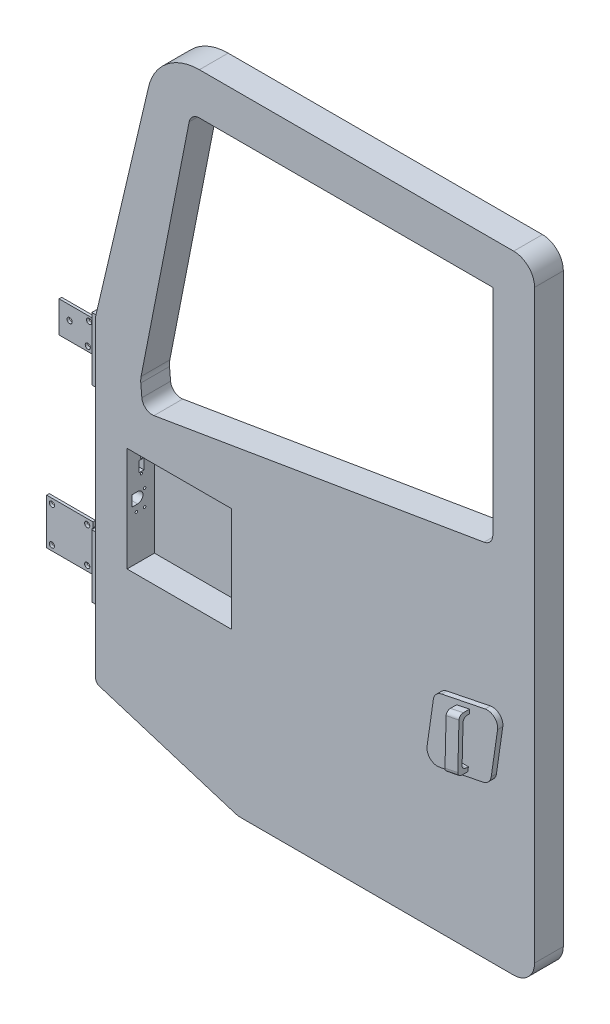
SolidWorks part; units mm, degrees
ref_plane "Front Plane" through (0, 0, 0) normal (0, 0, 1) x (1, 0, 0)
ref_plane "Top Plane" through (0, 0, 0) normal (0, 1, 0) x (1, 0, 0)
ref_plane "Right Plane" through (0, 0, 0) normal (1, 0, 0) x (0, 0, -1)
sketch "Sketch2" plane through (0, 0, 0) normal (0, 0, 1) x (1, 0, 0)
  line L1 (-179.7693, -762.022) -> (482.6, -762.022)
  line L3 (-281.2299, 761.978) -> (482.6, 761.978)
  line L4 (533.4, -711.222) -> (533.4, 711.178)
  line L5 (-459.8603, -656.939) -> (-452.0517, -645.784) construction
  line L6 (-417.9715, 597.0829) -> (44.2876, -63.266) construction
  line L8 (-524.4721, -657.2008) -> (-194.8579, -759.7295)
  line L9 (-306.1723, 639.7777) -> (-423.0219, 45.4039)
  line L10 (-423.7768, 31.1096) -> (-421.1458, 1.4921)
  line L14 (-281.2299, 660.378) -> (431.8, 660.378)
  line L16 (431.7996, 138.4174) -> (431.8, 660.378)
  line L17 (431.8, -660.422) -> (431.8, 660.378) construction
  line L18 (-172.0509, -660.422) -> (431.8, -660.422) construction
  line L19 (-533.4, 116.926) -> (-405.8883, 659.253)
  line L20 (-367.7549, -599.547) -> (-172.0509, -660.422) construction
  line L21 (-55.7209, -79.6007) -> (521.0599, 744.3665) construction
  line L22 (-306.1723, 639.7777) -> (-424.4164, 38.3105) construction
  line L23 (-424.4164, 38.3105) -> (-367.7549, -599.547) construction
  line L24 (-414.3579, -691.4526) -> (-194.8579, -759.7295) construction
  line L25 (-179.7693, -762.022) -> (482.6, -762.022)
  line L27 (-281.2299, 761.978) -> (482.6, 761.978)
  line L28 (533.4, -711.222) -> (533.4, 711.178)
  line L29 (-459.8603, -656.939) -> (-452.0517, -645.784) construction
  line L30 (-417.9715, 597.0829) -> (44.2876, -63.266) construction
  line L31 (-533.4, 116.926) -> (-466.2749, -638.723) construction
  line L32 (-391.6402, -21.3099) -> (410.6048, 113.3679)
  line L33 (-55.7209, -79.6007) -> (521.0599, 744.3665) construction
  line L34 (-281.2299, 761.978) -> (482.6, 761.978)
  line L35 (-533.4, 116.926) -> (-533.4, -645.074)
  line L36 (-179.7693, -762.022) -> (482.6, -762.022)
  line L37 (533.4, 711.178) -> (533.4, -711.222)
  line L38 (-417.9715, 597.0829) -> (44.2876, -63.266) construction
  line L39 (-471.5639, -673.6583) -> (-452.0517, -645.784) construction
  line L40 (-405.8883, 659.253) -> (-528.8132, 33.9764) construction
  line L41 (-55.7209, -79.6007) -> (521.0599, 744.3665) construction
  arc A0 (-405.8883, 659.253) -> (-281.2299, 761.978) centre (-281.2299, 634.978) cw
  arc A3 (533.4, 711.178) -> (482.6, 761.978) centre (482.6, 711.178) ccw
  arc A4 (482.6, -762.022) -> (533.4, -711.222) centre (482.6, -711.222) ccw
  arc A5 (-194.8579, -759.7295) -> (-179.7693, -762.022) centre (-179.7693, -711.222) ccw
  arc A7 (-367.7549, -599.547) -> (-367.7549, -599.547) centre (-367.7549, -599.547) ccw
  arc A8 (-172.0509, -660.422) -> (-172.0509, -660.422) centre (-172.0509, -660.422) ccw
  arc A9 (431.8, -660.422) -> (431.8, -660.422) centre (431.8, -660.422) ccw
  arc A10 (431.8, 660.378) -> (431.8, 660.378) centre (431.8, 660.378) ccw
  arc A11 (-306.1723, 639.7777) -> (-281.2299, 660.378) centre (-281.2299, 634.978) cw
  arc A12 (-423.0219, 45.4039) -> (-423.7768, 31.1096) centre (-373.176, 35.6045) ccw
  arc A13 (-424.4164, 38.3105) -> (-424.4164, 38.3105) centre (-424.4164, 38.3105) ccw construction
  arc A16 (-466.2749, -638.723) -> (-414.3579, -691.4526) centre (-391.0208, -616.5518) ccw construction
  arc A17 (-533.4, -645.074) -> (-524.4721, -657.2008) centre (-520.7, -645.074) ccw
  arc A18 (-528.8132, 33.9764) -> (-533.4, 116.926) centre (-501.9071, 77.0658) ccw construction
  arc A19 (431.7996, 138.4174) -> (410.6048, 113.3679) centre (406.3996, 138.4174) cw
  arc A20 (-391.6402, -21.3099) -> (-421.1458, 1.4921) centre (-395.8454, 3.7395) cw
  point P0 (0, 0)
  point P16 (-533.4, -0.0244)
  point P56 (0, 0)
  point P61 (0, 0)
  dimension "D3" = 127
  dimension "D6" = 50.8
  dimension "D8" = 50.8
  dimension "D2" = 12.7
  dimension "D9" = 25.4
  dimension "D1" = 1066.8
  dimension "D4" = 1524
  dimension "D5" = 762
  dimension "D7" = 101.6
extrude "Boss-Extrude1" add sketch "Sketch2" along normal mid plane 69.85 contours L8 A5 L1 A4 L4 A3 L3 A0 L10 A12 L9 A11 L14 L16 A20 region at (22.1716, -171.0663, 0)
ref_plane "bottom" through (0, -762.022, 0) normal (0, -1, 0) x (-1, 0, 0)
ref_plane "top door check" through (0, -158.772, 0) normal (0, -1, 0) x (-1, 0, 0)
ref_plane "door check mid" through (0, -176.2345, 0) normal (0, -1, 0) x (-1, 0, 0)
ref_plane "bottom door check" through (0, -193.697, 0) normal (0, -1, 0) x (-1, 0, 0)
ref_plane "top hinge top hole" through (0, 66.653, 0) normal (0, -1, 0) x (-1, 0, 0)
ref_plane "top hinge middle hole" through (0, 44.428, 0) normal (0, -1, 0) x (-1, 0, 0)
ref_plane "top hinge bottom hole" through (0, 12.678, 0) normal (0, -1, 0) x (-1, 0, 0)
ref_plane "bottome hinge top hole" through (0, -363.5595, 0) normal (0, -1, 0) x (-1, 0, 0)
ref_plane "bottom hinge bottom hole" through (0, -449.2845, 0) normal (0, -1, 0) x (-1, 0, 0)
ref_plane "Plane1" through (0, 0, 31.75) normal (0, 0, 1) x (1, 0, 0)
sketch "Sketch3" plane through (0, 0, 34.925) normal (0, 0, 1) x (1, 0, 0)
  line L0 (320.1959, -245.101) -> (425.9265, -223.6716)
  line L3 (314.9201, -401.6691) -> (420.6507, -380.2397)
  line L4 (456.113, -252.1835) -> (440.7462, -358.9639)
  line L5 (300.1004, -266.3768) -> (284.7336, -373.1572)
  line L6 (310.4001, -194.8067) -> (287.3499, -354.9772) construction
  line L7 (-487.6326, -408.8312) -> (533.4008, -201.8888) construction
  line L8 (-457.3598, -558.1943) -> (563.6737, -351.2518) construction
  line L9 (461.2461, -216.515) -> (438.1959, -376.6855) construction
  line L10 (373.0612, -234.3863) -> (367.7854, -390.9544) construction
  line L11 (360.2667, -236.9795) -> (354.9908, -393.5476)
  line L12 (385.8558, -231.7931) -> (380.58, -388.3612)
  line L13 (360.3684, -233.9586) -> (355.0926, -390.5267) construction
  line L14 (385.754, -234.814) -> (380.4782, -391.3821) construction
  arc A0 (300.1004, -266.3768) -> (320.1959, -245.101) centre (325.2414, -269.9949) cw
  arc A1 (284.7336, -373.1572) -> (314.9201, -401.6691) centre (309.8746, -376.7752) ccw
  arc A2 (440.7462, -358.9639) -> (420.6507, -380.2397) centre (415.6052, -355.3458) cw
  arc A3 (456.113, -252.1835) -> (425.9265, -223.6716) centre (430.972, -248.5655) ccw
  dimension "D3" = 25.4
  dimension "D1" = 152.4
  dimension "D2" = 152.4
  dimension "D4" = 12.7
  dimension "D5" = 12.7
extrude "Boss-Extrude2" add sketch "Sketch3" along normal blind 12.7 contours L5 A1 L3 L11 L0 A0 | L4 A3 L0 L12 L3 A2 | L12 L0 L11 L3 region at (325.2101, -323.7797, 34.925) region at (370.4233, -312.6704, 34.925) region at (415.6365, -301.561, 34.925)
sketch "Sketch5" plane through (0, 0, 34.925) normal (0, 0, 1) x (1, 0, 0)
  line L6 (-179.7693, -762.022) -> (482.6, -762.022)
  line L12 (-179.7693, -762.022) -> (482.6, -762.022)
  line L28 (387.9598, -243.0291) -> (384.7172, -375.8602)
  line L29 (353.4927, -382.1888) -> (356.7353, -249.3577)
  line L30 (387.9598, -243.0291) -> (356.7353, -249.3577)
  line L31 (384.7172, -375.8602) -> (353.4927, -382.1888)
  line L32 (320.1959, -245.101) -> (425.9265, -223.6716) construction
  line L33 (314.9201, -401.6691) -> (420.6507, -380.2397) construction
  line L34 (320.1959, -245.101) -> (425.9265, -223.6716) construction
  line L35 (314.9201, -401.6691) -> (420.6507, -380.2397) construction
  dimension "D2" = 11.43
  dimension "D3" = 11.43
  dimension "D1" = 0
extrude "Boss-Extrude4" add sketch "Sketch5" along normal blind 38.1 contours L31 L28 L30 L29 region at (370.7262, -312.609, 34.925)
sketch "Sketch6" plane through (393.6581, -9.61, 0) normal (0.9997, -0.0244, 0) x (0, 0, -1)
  line L9 (-47.625, -356.1994) -> (-62.865, -356.1994)
  line L10 (-62.865, -356.1994) -> (-62.865, -243.6487)
  line L11 (-62.865, -243.6487) -> (-47.625, -243.6487)
  line L12 (-47.625, -356.1994) -> (-62.865, -356.1994)
  line L13 (-62.865, -356.1994) -> (-62.865, -243.6487)
  line L14 (-62.865, -243.6487) -> (-47.625, -243.6487)
  line M5 (-47.625, -366.3594) -> (-47.625, -233.4887)
  dimension "D1" = 10.16
extrude "Cut-Extrude6" cut sketch "Sketch6" against normal through all and the other way through all contours L14 L13 L12 M5 region at (386.3385, -309.4447, 55.245)
fillet "Fillet5" radius 10.16 4 edges at (369.1049, -379.0245, 73.025) (369.4394, -365.3242, 62.865) (372.1861, -252.8071, 62.865) (372.3476, -246.1934, 73.025)
sketch "Sketch7" plane through (-533.4, 59.3738, 0) normal (1, 0, 0) x (0, 0, 1)
  line L0 (0, 821.3958) -> (0, -702.6042) construction
  line L1 (34.925, 821.3958) -> (-34.925, 821.3958) construction
  line L2 (34.925, -702.6042) -> (-34.925, -702.6042) construction
  line L4 (-31.75, -57.5522) -> (31.75, -57.5522)
  line L5 (-31.75, -57.5522) -> (-31.75, 94.8478)
  line L6 (-31.75, 94.8478) -> (31.75, 94.8478)
  line L11 (31.75, -57.5522) -> (31.75, 94.8478)
  line L12 (-31.75, -57.5522) -> (31.75, 94.8478) construction
  line L13 (-31.75, 94.8478) -> (31.75, -57.5522) construction
  line L19 (34.925, -57.5522) -> (-34.925, -57.5522) construction
  line L21 (-31.75, 552.0478) -> (31.75, 552.0478)
  line L28 (-31.75, 552.0478) -> (-31.75, 399.6478)
  line L29 (-31.75, 399.6478) -> (31.75, 399.6478)
  line L30 (31.75, 552.0478) -> (31.75, 399.6478)
  line L31 (-31.75, 552.0478) -> (31.75, 399.6478) construction
  line L32 (-31.75, 399.6478) -> (31.75, 552.0478) construction
  point P6 (0, 18.6478)
  point P13 (0, 475.8478)
  dimension "D1" = 63.5
  dimension "D2" = 152.4
  dimension "D4" = 304.8
extrude "Boss-Extrude5" add sketch "Sketch7" against normal blind 12.7
sketch "Sketch16" plane through (0, 0, 34.925) normal (0, 0, 1) x (1, 0, 0)
  line L1 (-457.2, -122.9099) -> (-457.2, -376.9099)
  line L3 (-203.2, -376.9099) -> (-203.2, -122.9099)
  line L5 (-533.4, 116.926) -> (-533.4, -645.074) construction
  line L6 (-457.2, -122.9099) -> (-203.2, -122.9099)
  line L7 (-457.2, -376.9099) -> (-203.2, -376.9099)
  dimension "D1" = 254
  dimension "D2" = 101.6
  dimension "D3" = 254
  dimension "D4" = 76.2
extrude "Cut-Extrude8" cut sketch "Sketch16" against normal blind 66.675
sketch "Sketch20" plane through (-533.4, 0, 0) normal (-1, 0, 0) x (0, 0, 1)
  line L0 (-38.4175, -176.2345) -> (38.4175, -176.2345) construction
  line L1 (-6.35, -188.9345) -> (6.35, -188.9345)
  line L2 (-6.35, -188.9345) -> (-6.35, -163.5345)
  line L3 (-6.35, -163.5345) -> (6.35, -163.5345)
  line L4 (6.35, -188.9345) -> (6.35, -163.5345)
  line L5 (-6.35, -188.9345) -> (6.35, -163.5345) construction
  line L6 (-6.35, -163.5345) -> (6.35, -188.9345) construction
  line L7 (-38.4175, -158.772) -> (38.4175, -158.772) construction
  line L8 (6.35, -176.2345) -> (-6.35, -176.2345) construction
  circle A0 centre (0, -158.772) radius 2.54
  circle A1 centre (0, -193.697) radius 2.54
  point P0 (0, -176.2345)
  dimension "D3" = 5.08
  dimension "D1" = 12.7
  dimension "D2" = 25.4
extrude "Cut-Extrude12" cut sketch "Sketch20" against normal up to surface (76.2 mm away) contours A0 | L4 L3 L2 L1 | A1 up to face at (-457.2, -249.9099, 1.5875)
sketch "Sketch21" plane through (0, 0, 0) normal (0, 0, 1) x (1, 0, 0)
  line L0 (-38.4175, 66.653) -> (38.4175, 66.653) construction
  line L1 (-202.423, 66.653) -> (-1027.3811, 66.653) construction
  line L2 (-212.5576, 44.428) -> (-1027.3811, 44.428) construction
  line L3 (-38.4175, 44.428) -> (38.4175, 44.428) construction
  line L4 (-212.5576, 12.678) -> (-1027.3811, 12.678) construction
  line L5 (-38.4175, 12.678) -> (38.4175, 12.678) construction
  line L6 (-546.1, 116.926) -> (-546.1, -35.474) construction
  line L7 (-558.8, 66.653) -> (-546.1, 66.653)
  line L8 (-558.8, 66.653) -> (-558.8, 12.678)
  line L9 (-558.8, 12.678) -> (-546.1, 12.678)
  line L10 (-546.1, 66.653) -> (-546.1, 12.678)
  line L11 (-654.05, 77.448) -> (-654.05, 1.248)
  line L12 (-654.05, 77.448) -> (-558.8, 77.448)
  line L15 (-558.8, 77.448) -> (-558.8, 12.678)
  line L16 (-654.05, 77.448) -> (-558.8, 12.678) construction
  line L17 (-654.05, 10.0872) -> (-558.8, 77.448) construction
  line L18 (-654.05, 1.248) -> (-558.8, 1.248)
  line L19 (-558.8, 12.678) -> (-558.8, 1.248)
  circle A0 centre (-584.2, 12.678) radius 6.35
  circle A1 centre (-628.65, 44.428) radius 6.35
  circle A2 centre (-581.025, 66.653) radius 6.35
  point P18 (-605.4912, 44.428)
  dimension "D2" = 12.7
  dimension "D3" = 25.4
  dimension "D4" = 69.85
  dimension "D5" = 22.225
  dimension "D6" = 95.25
  dimension "D9" = 64.77
  dimension "D1" = 12.7
  dimension "D7" = 76.2
  dimension "D8" = 33.02
extrude "Boss-Extrude8" add sketch "Sketch21" along normal mid plane 6.35 contours L19 L8 L15 L12 L11 L18 A2 A1 A0 | L10 L7 L8 L9 region at (-552.45, 39.6655, 0) region at (-606.8928, 39.2427, 0)
sketch "Sketch26" plane through (0, 0, 0) normal (0, 0, 1) x (1, 0, 0)
  line L0 (-193.6896, -363.5595) -> (-881.8717, -363.5595) construction
  line L1 (-38.4175, -363.5595) -> (38.4175, -363.5595) construction
  line L2 (-133.4597, -449.2845) -> (-881.8717, -449.2845) construction
  line L3 (-38.4175, -449.2845) -> (38.4175, -449.2845) construction
  line L4 (-625.8948, -363.5595) -> (-625.8948, -449.2845) construction
  line L5 (-625.8948, -406.422) -> (-892.4677, -406.422) construction
  line L6 (-546.1, -340.274) -> (-546.1, -492.674) construction
  line L7 (-571.5, -449.2845) -> (-546.1, -449.2845)
  line L8 (-571.5, -449.2845) -> (-571.5, -363.5595)
  line L9 (-571.5, -363.5595) -> (-546.1, -363.5595)
  line L10 (-546.1, -449.2845) -> (-546.1, -363.5595)
  line L11 (-571.5, -449.2845) -> (-546.1, -363.5595) construction
  line L12 (-571.5, -363.5595) -> (-546.1, -449.2845) construction
  point P12 (-558.8, -406.422)
  dimension "D1" = 25.4
extrude "Boss-Extrude12" add sketch "Sketch26" along normal mid plane 12.7
sketch "Sketch27" plane through (0, 0, 0) normal (0, 0, 1) x (1, 0, 0)
  line L0 (-211.2814, -363.5595) -> (-919.4505, -363.5595) construction
  line L1 (-38.4175, -363.5595) -> (38.4175, -363.5595) construction
  line L2 (-201.3631, -449.2845) -> (-928.7076, -449.2845) construction
  line L3 (-38.4175, -449.2845) -> (38.4175, -449.2845) construction
  line L4 (-571.5, -363.5595) -> (-571.5, -449.2845) construction
  line L5 (-631.7994, -363.5595) -> (-631.7994, -449.2845) construction
  line L6 (-631.7994, -406.422) -> (-919.4505, -406.422) construction
  line L8 (-684.2125, -461.9845) -> (-571.5, -461.9845)
  line L9 (-684.2125, -461.9845) -> (-684.2125, -350.8595)
  line L10 (-684.2125, -350.8595) -> (-571.5, -350.8595)
  line L11 (-571.5, -461.9845) -> (-571.5, -350.8595)
  line L12 (-684.2125, -461.9845) -> (-571.5, -350.8595) construction
  line L13 (-684.2125, -350.8595) -> (-571.5, -461.9845) construction
  circle A0 centre (-585.7875, -363.5595) radius 6.35
  circle A2 centre (-671.5125, -449.2845) radius 6.35
  circle A4 centre (-585.7875, -449.2845) radius 6.35
  circle A5 centre (-671.5125, -363.5595) radius 6.35
  point P22 (-627.8563, -406.422)
  dimension "D1" = 12.7
  dimension "D2" = 100.0125
  dimension "D3" = 14.2875
  dimension "D4" = 12.7
extrude "Boss-Extrude13" add sketch "Sketch27" along normal mid plane 6.35
sketch "Sketch28" plane through (-533.4, 0, 0) normal (-1, 0, 0) x (0, 0, 1)
  line L1 (9.225, -226.7946) -> (22.225, -226.7946)
  line L3 (9.225, -252.7946) -> (22.225, -252.7946)
  line L4 (22.225, -226.7946) -> (22.225, -252.7946)
  line L5 (34.925, -245.101) -> (34.925, -223.6716) construction
  arc A6 (9.225, -226.7946) -> (9.225, -252.7946) centre (9.225, -239.7946) ccw
  circle A7 centre (-7.705, -228.0446) radius 3
  circle A8 centre (-7.705, -268.0446) radius 3
  circle A9 centre (12.295, -268.0446) radius 3
  point P7 (-3.775, -239.7946)
  dimension "D4" = 40
  dimension "D5" = 26
  dimension "D6" = 26
  dimension "D1" = 11.75
  dimension "D2" = 3.93
  dimension "D3" = 20
  dimension "D8" = 12.7
  dimension "D7" = 6
  dimension "D9" = 13
extrude "Cut-Extrude13" cut sketch "Sketch28" against normal up to surface (76.2 mm away) contours L1 A6 L3 L4 | A8 | A9 | A7 region at (-533.4, -239.7946, 10.4385) region at (-533.4, -268.0446, -7.705) region at (-533.4, -268.0446, 12.295) up to face at (-457.2, -176.2345, 0)
equation "\"doorwidth\"= 42in"
equation "\"D1@Sketch2\"=\"doorwidth\""
equation "\"doorheight\"= 60in"
equation "\"D4@Sketch2\"=\"doorheight\""
equation "\"doorthickness\"= 2.75in"
equation "\"D1@Boss-Extrude1\"=\"doorthickness\""
equation "\"hingewidth\"= 2.5in"
equation "\"hingeheight\"= 6in"
equation "\"distanceofhinges\"= 12in"
equation "\"D1@Sketch7\"=\"hingewidth\""
equation "\"D2@Sketch7\"=\"hingeheight\""
equation "\"D4@Sketch7\"=\"distanceofhinges\""
